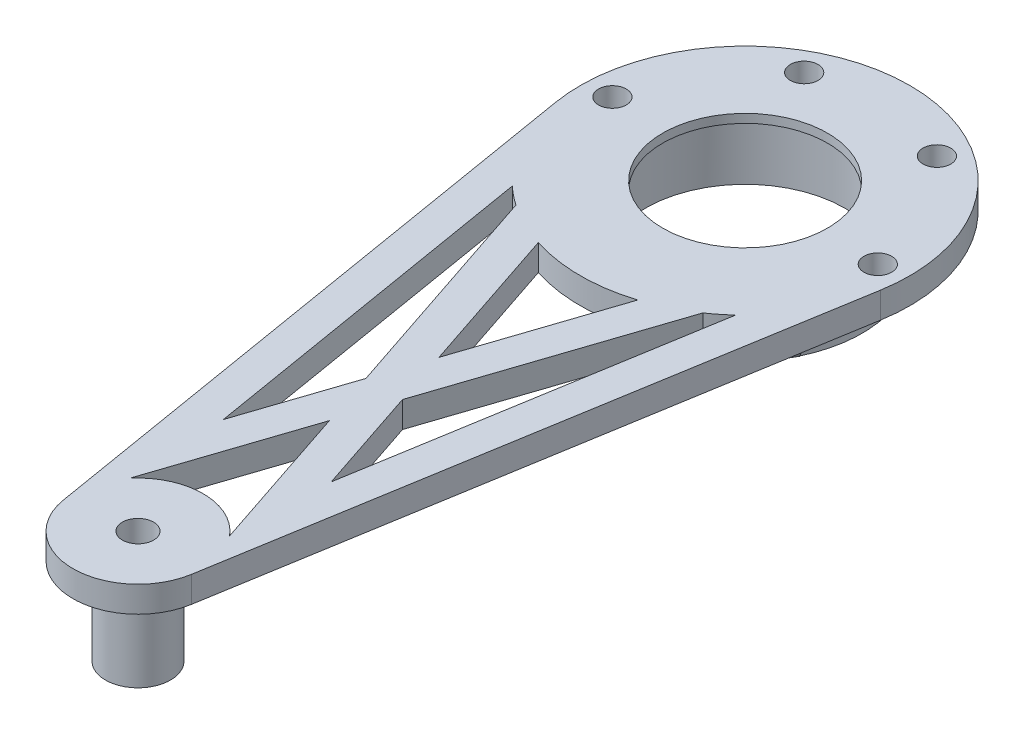
SolidWorks part; units mm, degrees
ref_plane "Front Plane" through (0, 0, 0) normal (0, 0, 1) x (1, 0, 0)
ref_plane "Top Plane" through (0, 0, 0) normal (0, 1, 0) x (1, 0, 0)
ref_plane "Right Plane" through (0, 0, 0) normal (1, 0, 0) x (0, 0, -1)
sketch "Sketch1" plane through (0, 0, 0) normal (0, 1, 0) x (1, 0, 0)
  circle A0 centre (0, 0) radius 3.75
  dimension "D1" = 7.5
extrude "Boss-Extrude1" add sketch "Sketch1" along normal blind 10
sketch "Sketch2" plane through (0, 10, 0) normal (0, 1, 0) x (1, 0, 0)
  line L0 (-18.7418, 66.8786) -> (-7.3981, -1.2321)
  line L1 (18.7418, 66.8786) -> (7.3981, -1.2321)
  line L2 (-12.8803, 56.0323) -> (-6.2225, 16.0572)
  line L3 (12.8803, 56.0323) -> (6.2225, 16.0572)
  line L4 (-10.7711, 54.348) -> (-2.1084, 28.3868)
  line L5 (-5.7326, 51.8854) -> (0, 34.7055)
  line L6 (0, 70) -> (0, 34.7055) construction
  line L7 (10.7711, 54.348) -> (2.1084, 28.3868)
  line L8 (5.7326, 51.8854) -> (0, 34.7055)
  line L9 (-2.1084, 28.3868) -> (-6.2225, 16.0572)
  line L10 (0, 22.0681) -> (0, 0) construction
  line L11 (0, 22.0681) -> (-5.7614, 4.8017)
  line L12 (2.1084, 28.3868) -> (6.2225, 16.0572)
  line L13 (0, 22.0681) -> (5.7614, 4.8017)
  arc A0 (-7.3981, -1.2321) -> (7.3981, -1.2321) centre (0, 0) ccw
  circle A1 centre (0, 70) radius 11.5
  arc A2 (-12.8803, 56.0323) -> (-10.7711, 54.348) centre (0, 70) ccw
  arc A3 (18.7418, 66.8786) -> (-18.7418, 66.8786) centre (0, 70) ccw
  arc A4 (5.7614, 4.8017) -> (-5.7614, 4.8017) centre (0, 0) ccw
  arc A5 (-5.7326, 51.8854) -> (5.7326, 51.8854) centre (0, 70) ccw
  arc A6 (10.7711, 54.348) -> (12.8803, 56.0323) centre (0, 70) ccw
  circle M10 centre (0, 0) radius 3.75
  dimension "D1" = 15
  dimension "D2" = 23
  dimension "D7" = 7.5
  dimension "D3" = 70
  dimension "D4" = 4
  dimension "D5" = 4
  dimension "D6" = 4
extrude "Boss-Extrude2" add sketch "Sketch2" along normal blind 3 contours L1 A3 L0 A0 L5 A2 L8 L4 L9 L2 L12 L7 L3 A1 L13 A4 L11 M10 | M10 region at (0, 10, -87.9629) region at (0, 10, 0)
sketch "Sketch3" plane through (0, 13, 0) normal (0, 1, 0) x (1, 0, 0)
  circle A0 centre (0, 70) radius 11.5
  circle A1 centre (0, 70) radius 9.5
  circle A2 centre (0, 70) radius 11.5 construction
  dimension "D1" = 2
extrude "Boss-Extrude3" add sketch "Sketch3" against normal blind 1
sketch "Sketch4" plane through (0, 10, 0) normal (0, -1, 0) x (1, 0, 0)
  circle A0 centre (0, -70) radius 11.5
  circle A1 centre (0, -70) radius 13.5
  circle A2 centre (0, -70) radius 11.5 construction
  dimension "D1" = 2
extrude "Boss-Extrude4" add sketch "Sketch4" along normal blind 5.5
sketch "Sketch5" plane through (0, 10, 0) normal (0, -1, 0) x (1, 0, 0)
  line L5 (-1, -53.5) -> (1, -53.5)
  line L6 (-1, -53.5) -> (-1, -58.5)
  line L7 (-1, -58.5) -> (1, -58.5)
  line L8 (1, -53.5) -> (1, -58.5)
  circle A1 centre (0, -70) radius 11.5 construction
  circle A2 centre (0, -70) radius 7.2102
  circle A3 centre (0, -70) radius 9.5 construction
  point P8 (0, -53.5)
  dimension "D1" = 2
  dimension "D2" = 5
extrude "Boss-Extrude5" add sketch "Sketch5" along normal up to surface (5.5 mm away) contours L6 L7 L8 L5 up to face at (0, 4.5, -83.5)
chamfer "Chamfer1" distance 3 angle 56 1 edges at (0, 4.5, -53.5) first distance on face at (0, 4.5, -61.7593)
pattern_circular "CirPattern1" count 6 over 360 about axis through (0, 13, -70) along (0, -1, 0) of "Boss-Extrude5", "Chamfer1" reverse direction yes
sketch "Sketch6" plane through (0, 10, 0) normal (0, -1, 0) x (1, 0, 0)
  circle A0 centre (-16, -70.6994) radius 1.6
  circle A1 centre (0, -70) radius 9.5 construction
  dimension "D1" = 3.2
  dimension "D2" = 16
extrude "Cut-Extrude1" cut sketch "Sketch6" against normal through all
pattern_circular "CirPattern2" count 6 over 360 about axis through (0, 4.5, -70) along (0, -1, 0) skipping 4, 5 of "Cut-Extrude1"
sketch "Sketch7" plane through (0, 0, 0) normal (0, -1, 0) x (-1, 0, 0)
  circle A0 centre (0, 0) radius 1.8
  dimension "D1" = 3.6
extrude "Cut-Extrude2" cut sketch "Sketch7" against normal through all contours A0
